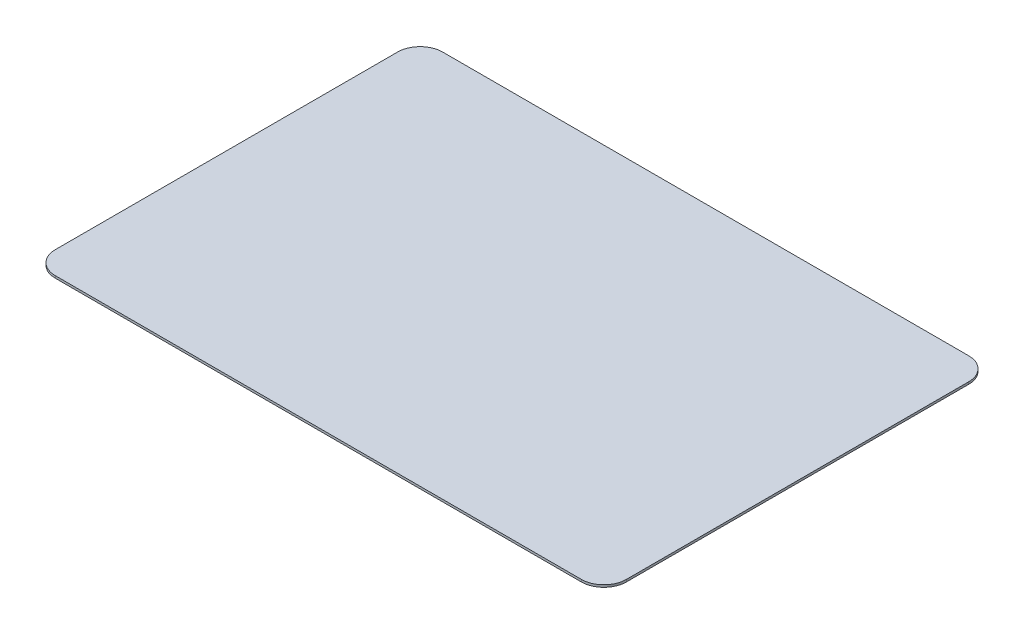
SolidWorks part; units mm, degrees
ref_plane "Front Plane" through (0, 0, 0) normal (0, 0, 1) x (1, 0, 0)
ref_plane "Top Plane" through (0, 0, 0) normal (0, 1, 0) x (1, 0, 0)
ref_plane "Right Plane" through (0, 0, 0) normal (1, 0, 0) x (0, 0, -1)
sketch "Sketch1" plane through (0, 0, 0) normal (0, 1, 0) x (1, 0, 0)
  line L1 (-127, 86.135) -> (127, 86.135)
  line L2 (-127, 86.135) -> (-127, -86.135)
  line L3 (-127, -86.135) -> (127, -86.135)
  line L4 (127, 86.135) -> (127, -86.135)
  line L5 (-127, 86.135) -> (127, -86.135) construction
  line L6 (-127, -86.135) -> (127, 86.135) construction
  point P0 (0, 0)
  dimension "D1" = 254
  dimension "D2" = 172.27
extrude "Boss-Extrude1" add sketch "Sketch1" along normal blind 1
fillet "Fillet1" radius 10 4 edges at (-127, 0.5, 86.135) (127, 0.5, 86.135) (127, 0.5, -86.135) (-127, 0.5, -86.135)
